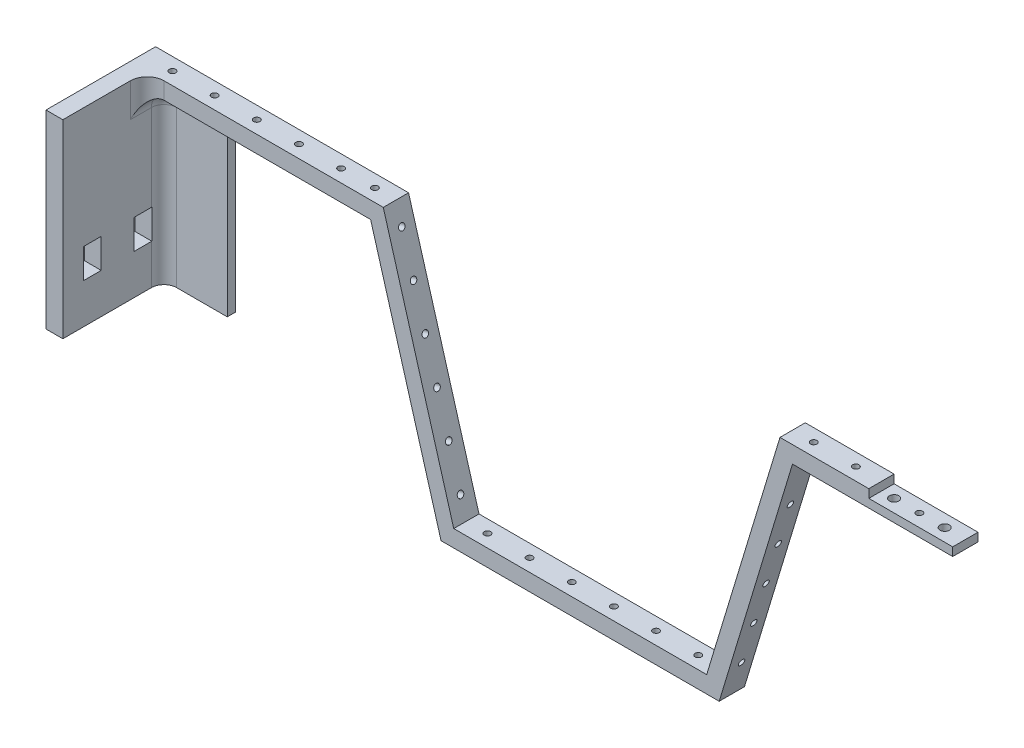
SolidWorks part; units mm, degrees
ref_plane "Front Plane" through (0, 0, 0) normal (0, 0, 1) x (1, 0, 0)
ref_plane "Top Plane" through (0, 0, 0) normal (0, 1, 0) x (1, 0, 0)
ref_plane "Right Plane" through (0, 0, 0) normal (1, 0, 0) x (0, 0, -1)
sketch "Sketch1" plane through (0, 0, 0) normal (0, 0, 1) x (1, 0, 0)
  line L0 (-23.7058, 144.923) -> (-23.7058, 142.923)
  line L1 (-23.6058, 144.923) -> (-43.6058, 144.923) construction
  line L2 (-23.7058, 142.923) -> (-61.7058, 142.923)
  line L3 (-61.7058, 142.923) -> (-79.0939, 85.4978)
  line L4 (-79.0939, 85.4978) -> (-145.0669, 85.4978)
  line L5 (-145.0669, 85.4978) -> (-161.7783, 143.1235)
  line L6 (-161.7783, 143.1235) -> (-214.7735, 143.1235)
  line L7 (-214.7735, 143.1235) -> (-214.7735, 102.1235)
  line L8 (-214.7735, 102.1235) -> (-218.7735, 102.1235)
  line L9 (-218.7735, 102.1235) -> (-218.7735, 147.1235)
  line L10 (-218.7735, 147.1235) -> (-158.7735, 147.1235)
  line L11 (-158.7735, 147.1235) -> (-142.0621, 89.4978)
  line L12 (-142.0621, 89.4978) -> (-82.0621, 89.4978)
  line L13 (-82.0621, 89.4978) -> (-64.674, 146.923)
  line L14 (-64.674, 146.923) -> (-43.6058, 146.923)
  line L15 (-43.6058, 146.923) -> (-43.6058, 144.923)
  line L16 (-43.6058, 144.923) -> (-23.7058, 144.923)
  dimension "D1" = 38
  dimension "D2" = 60
  dimension "D3" = 60
  dimension "D4" = 60
  dimension "D5" = 60
  dimension "D6" = 2
  dimension "D7" = 2
  dimension "D8" = 4
  dimension "D9" = 4
  dimension "D10" = 4
  dimension "D11" = 4
  dimension "D12" = 4
  dimension "D13" = 45
  dimension "D14" = 19.9
extrude "Boss-Extrude1" add sketch "Sketch1" along normal blind 6
sketch "Sketch2" plane through (0, 144.923, 0) normal (0, 1, 0) x (1, 0, 0)
  line L0 (-23.7058, -6) -> (-23.7058, 0) construction
  line L1 (-23.7058, -6) -> (-43.6058, -6) construction
  circle A0 centre (-28.6058, -3) radius 1.1
  circle A1 centre (-40.6058, -3) radius 1.1
  dimension "D1" = 2.2
  dimension "D2" = 2.2
  dimension "D3" = 4.9
  dimension "D4" = 3
  dimension "D5" = 3
  dimension "D6" = 16.9
extrude "Cut-Extrude1" cut sketch "Sketch2" against normal blind 6
sketch "Sketch3" plane through (0, 144.923, 0) normal (0, 1, 0) x (1, 0, 0)
  circle A0 centre (-34.6058, -3) radius 0.75
extrude "Cut-Extrude2" cut sketch "Sketch3" against normal blind 6
sketch "Sketch4" plane through (0, 146.923, 0) normal (0, 1, 0) x (1, 0, 0)
  line L0 (-43.6058, -6) -> (-64.674, -6) construction
  line L1 (-64.674, -6) -> (-64.674, 0) construction
  circle A0 centre (-59.674, -3) radius 0.75
  circle A1 centre (-49.674, -3) radius 0.75
  dimension "D1" = 1.5
  dimension "D2" = 3
  dimension "D3" = 5
  dimension "D4" = 1.5
  dimension "D5" = 3
  dimension "D6" = 15
extrude "Cut-Extrude3" cut sketch "Sketch4" against normal blind 6
sketch "Sketch5" plane through (-99.9937, 30.2776, 0) normal (-0.9571, 0.2898, 0) x (0, 0, 1)
  line L0 (6, 121.8754) -> (6, 61.8754) construction
  line L1 (6, 121.8754) -> (0, 121.8754) construction
  circle A0 centre (3, 116.8754) radius 0.75
  circle A1 centre (3, 106.8754) radius 0.75
  circle A2 centre (3, 96.8754) radius 0.75
  circle A3 centre (3, 86.8754) radius 0.75
  circle A4 centre (3, 76.8754) radius 0.75
  circle A5 centre (3, 66.8754) radius 0.75
  dimension "D1" = 1.5
  dimension "D2" = 3
  dimension "D3" = 5
  dimension "D4" = 6
extrude "Cut-Extrude4" cut sketch "Sketch5" against normal blind 6
sketch "Sketch6" plane through (0, 89.4978, 0) normal (0, 1, 0) x (1, 0, 0)
  line L0 (-82.0621, -6) -> (-142.0621, -6) construction
  line L1 (-82.0621, -6) -> (-82.0621, 0) construction
  circle A0 centre (-87.0621, -3) radius 0.75
  circle A1 centre (-97.0621, -3) radius 0.75
  circle A2 centre (-107.0621, -3) radius 0.75
  circle A3 centre (-117.0621, -3) radius 0.75
  circle A4 centre (-127.0621, -3) radius 0.75
  circle A5 centre (-137.0621, -3) radius 0.75
  dimension "D1" = 1.5
  dimension "D2" = 3
  dimension "D3" = 5
  dimension "D4" = 6
extrude "Cut-Extrude5" cut sketch "Sketch6" against normal blind 6
sketch "Sketch7" plane through (-107.1006, -31.0592, 0) normal (0.9604, 0.2785, 0) x (0, 0, -1)
  line L0 (0, 125.524) -> (0, 185.524) construction
  line L1 (-6, 185.524) -> (0, 185.524) construction
  circle A0 centre (-3, 180.524) radius 0.75
  circle A1 centre (-3, 170.524) radius 0.75
  circle A2 centre (-3, 160.524) radius 0.75
  circle A3 centre (-3, 150.524) radius 0.75
  circle A4 centre (-3, 140.524) radius 0.75
  circle A5 centre (-3, 130.524) radius 0.75
  dimension "D1" = 1.5
  dimension "D2" = 3
  dimension "D3" = 5
  dimension "D4" = 6
extrude "Cut-Extrude6" cut sketch "Sketch7" against normal blind 6
sketch "Sketch8" plane through (0, 147.1235, 0) normal (0, 1, 0) x (1, 0, 0)
  line L0 (-158.7735, 0) -> (-218.7735, 0) construction
  line L1 (-218.7735, -6) -> (-218.7735, 0) construction
  circle A0 centre (-211.7735, -3) radius 0.75
  circle A1 centre (-201.7735, -3) radius 0.75
  circle A2 centre (-191.7735, -3) radius 0.75
  circle A3 centre (-181.7735, -3) radius 0.75
  circle A4 centre (-171.7735, -3) radius 0.75
  dimension "D1" = 1.5
  dimension "D2" = 3
  dimension "D3" = 7
  dimension "D4" = 5
extrude "Cut-Extrude7" cut sketch "Sketch8" against normal blind 6
sketch "Sketch9" plane through (0, 147.1235, 0) normal (0, 1, 0) x (1, 0, 0)
  line L0 (-158.7735, -6) -> (-158.7735, 0) construction
  line L1 (-158.7735, -6) -> (-218.7735, -6) construction
  circle A0 centre (-163.7735, -3) radius 0.75
  dimension "D1" = 1.5
  dimension "D2" = 5
  dimension "D3" = 3
extrude "Cut-Extrude8" cut sketch "Sketch9" against normal blind 6
sketch "Sketch12" plane through (-218.7735, 0, 0) normal (-1, 0, 0) x (0, 0, 1)
  line L1 (6, 147.1235) -> (26, 147.1235)
  line L2 (6, 147.1235) -> (6, 102.1235)
  line L3 (6, 102.1235) -> (26, 102.1235)
  line L4 (26, 147.1235) -> (26, 102.1235)
  dimension "D1" = 20
  dimension "D2" = 45
extrude "Boss-Extrude5" add sketch "Sketch12" against normal blind 4
fillet "Fillet4" radius 4 2 edges at (-214.7735, 143.1235, 3) (-214.7735, 145.1235, 6)
sketch "Sketch13" plane through (0, 0, 0) normal (0, 0, -1) x (-1, 0, 0)
  line L1 (218.7735, 147.1235) -> (199.7735, 147.1235)
  line L2 (218.7735, 147.1235) -> (218.7735, 102.1235)
  line L3 (218.7735, 102.1235) -> (199.7735, 102.1235)
  line L4 (199.7735, 147.1235) -> (199.7735, 102.1235)
  dimension "D1" = 19
  dimension "D2" = 45
extrude "Boss-Extrude6" add sketch "Sketch13" against normal blind 2
fillet "Fillet5" radius 3 4 edges at (-205.2735, 143.1235, 2) (-213.602, 141.952, 2) (-199.7735, 143.1235, 1) (-214.7735, 120.6235, 2)
sketch "Sketch14" plane through (-218.7735, 0, 0) normal (-1, 0, 0) x (0, 0, 1)
  line L0 (26, 102.1235) -> (0, 102.1235) construction
  line L1 (4.9, 118.6235) -> (9.1, 118.6235)
  line L2 (4.9, 118.6235) -> (4.9, 111.6235)
  line L3 (4.9, 111.6235) -> (9.1, 111.6235)
  line L4 (9.1, 118.6235) -> (9.1, 111.6235)
  line L5 (16.9, 118.6235) -> (21.1, 118.6235)
  line L6 (16.9, 118.6235) -> (16.9, 111.6235)
  line L7 (16.9, 111.6235) -> (21.1, 111.6235)
  line L8 (21.1, 118.6235) -> (21.1, 111.6235)
  line L9 (26, 102.1235) -> (26, 147.1235) construction
  line L10 (0, 147.1235) -> (0, 102.1235) construction
  dimension "D1" = 4.2
  dimension "D2" = 4.2
  dimension "D3" = 7
  dimension "D4" = 7
  dimension "D5" = 16.5
  dimension "D6" = 9.5
  dimension "D7" = 4.9
  dimension "D8" = 4.9
extrude "Cut-Extrude10" cut sketch "Sketch14" against normal blind 12
